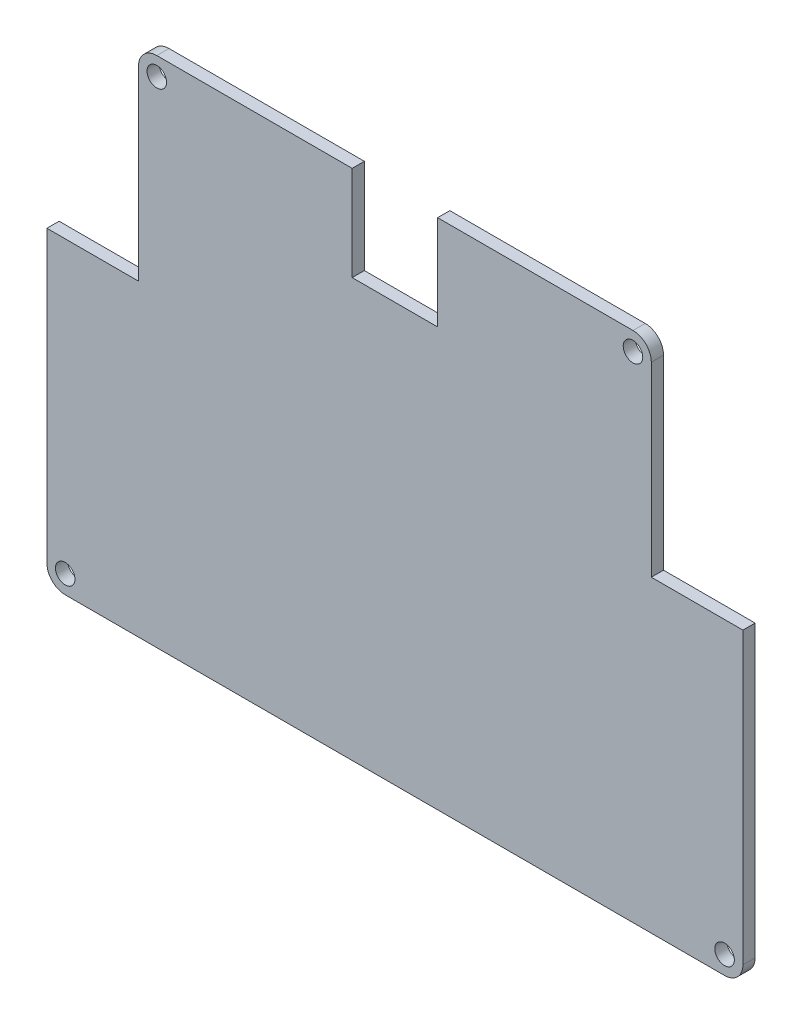
SolidWorks part; units mm, degrees
ref_plane "Front Plane" through (0, 0, 0) normal (0, 0, 1) x (1, 0, 0)
ref_plane "Top Plane" through (0, 0, 0) normal (0, 1, 0) x (1, 0, 0)
ref_plane "Right Plane" through (0, 0, 0) normal (1, 0, 0) x (0, 0, -1)
other "Centro da massa"
sketch "Sketch1" plane through (0, 0, 0) normal (0, 0, 1) x (1, 0, 0)
  line L0 (-42, 25.4696) -> (-57, 25.4696)
  line L1 (57, 25.4696) -> (42, 25.4696)
  line L2 (57, 25.4696) -> (57, -22.0304)
  line L3 (54, -25.0304) -> (-54, -25.0304)
  line L4 (-57, 25.4696) -> (-57, -22.0304)
  line L5 (57, 25.4696) -> (-55.3258, -24.7215) construction
  line L6 (55.3258, -24.7215) -> (-57, 25.4696) construction
  line L8 (-42, 25.4696) -> (-42, 55.9696)
  line L9 (-39, 58.9696) -> (-7, 58.9696)
  line L10 (42, 25.4696) -> (42, 55.9696)
  line L11 (-42, 25.4696) -> (40.7091, 58.4351) construction
  line L12 (-40.7091, 58.4351) -> (42, 25.4696) construction
  line L13 (7, 58.9696) -> (39, 58.9696)
  line L15 (-7, 58.9696) -> (-7, 43.4696)
  line L16 (-7, 43.4696) -> (7, 43.4696)
  line L17 (7, 58.9696) -> (7, 43.4696)
  line L18 (-7, 58.9696) -> (7, 43.4696) construction
  line L19 (-7, 43.4696) -> (7, 58.9696) construction
  line L20 (0, -1.1) -> (0, 1.1) construction
  arc A0 (57, -22.0304) -> (54, -25.0304) centre (54, -22.0304) cw
  circle A1 centre (54, -22.0304) radius 1.6
  circle A4 centre (-54, -22.0304) radius 1.6
  arc A5 (-57, -22.0304) -> (-54, -25.0304) centre (-54, -22.0304) ccw
  arc A8 (42, 55.9696) -> (39, 58.9696) centre (39, 55.9696) ccw
  circle A9 centre (39, 55.9696) radius 1.6
  arc A10 (-42, 55.9696) -> (-39, 58.9696) centre (-39, 55.9696) cw
  circle A11 centre (-39, 55.9696) radius 1.6
  point P0 (0, 0)
  point P6 (0, 42.2096)
  point P11 (0, 51.2196)
  dimension "D7" = 3
  dimension "D8" = 3.2
  dimension "D2" = 3
  dimension "D11" = 3.2
  dimension "D3" = 15
  dimension "D4" = 84
  dimension "D5" = 68.5
  dimension "D6" = 50
  dimension "D9" = 114
  dimension "D10" = 50.5
extrude "Boss-Extrude1" add sketch "Sketch1" along normal blind 2
